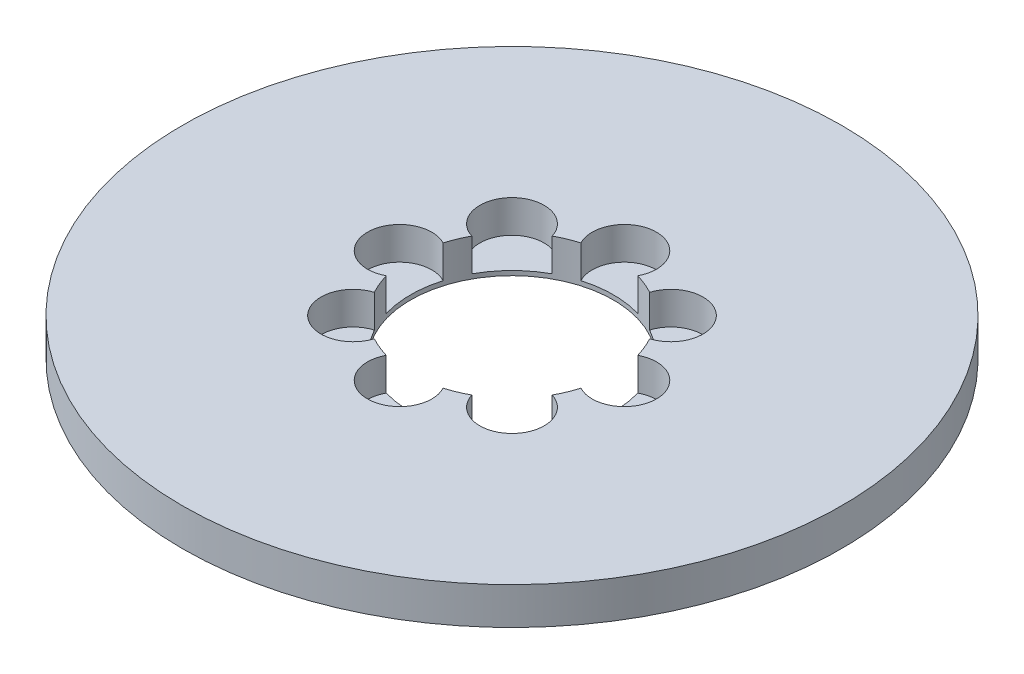
SolidWorks part; units mm, degrees
ref_plane "Front Plane" through (0, 0, 0) normal (0, 0, 1) x (1, 0, 0)
ref_plane "Top Plane" through (0, 0, 0) normal (0, 1, 0) x (1, 0, 0)
ref_plane "Right Plane" through (0, 0, 0) normal (1, 0, 0) x (0, 0, -1)
sketch "Sketch1" plane through (0, 0, 0) normal (0, 1, 0) x (1, 0, 0)
  circle A0 centre (0, 0) radius 97.5
  dimension "FLANGE_OD" = 195
extrude "Boss-Extrude1" add sketch "Sketch1" along normal blind 11
sketch "Sketch2" plane through (0, 0, 0) normal (0, 1, 0) x (1, 0, 0)
  circle A0 centre (0, 0) radius 30
  dimension "BORE_D" = 60
extrude "Cut-Extrude1" cut sketch "Sketch2" along normal through all
sketch "Sketch3" plane through (0, 11, 0) normal (0, 1, 0) x (1, 0, 0)
  circle A0 centre (0, 0) radius 33.235 construction
  circle A1 centre (-33.235, 0) radius 9.5124
  dimension "BOLT_D" = 19.0249
  dimension "BOLT_PCD" = 66.47
extrude "Cut-Extrude2" cut sketch "Sketch3" against normal blind 9.6663
pattern_circular "CirPattern1" count 8 over 360 about axis through (0, 0, 0) along (0, 1, 0) of "Cut-Extrude2"
